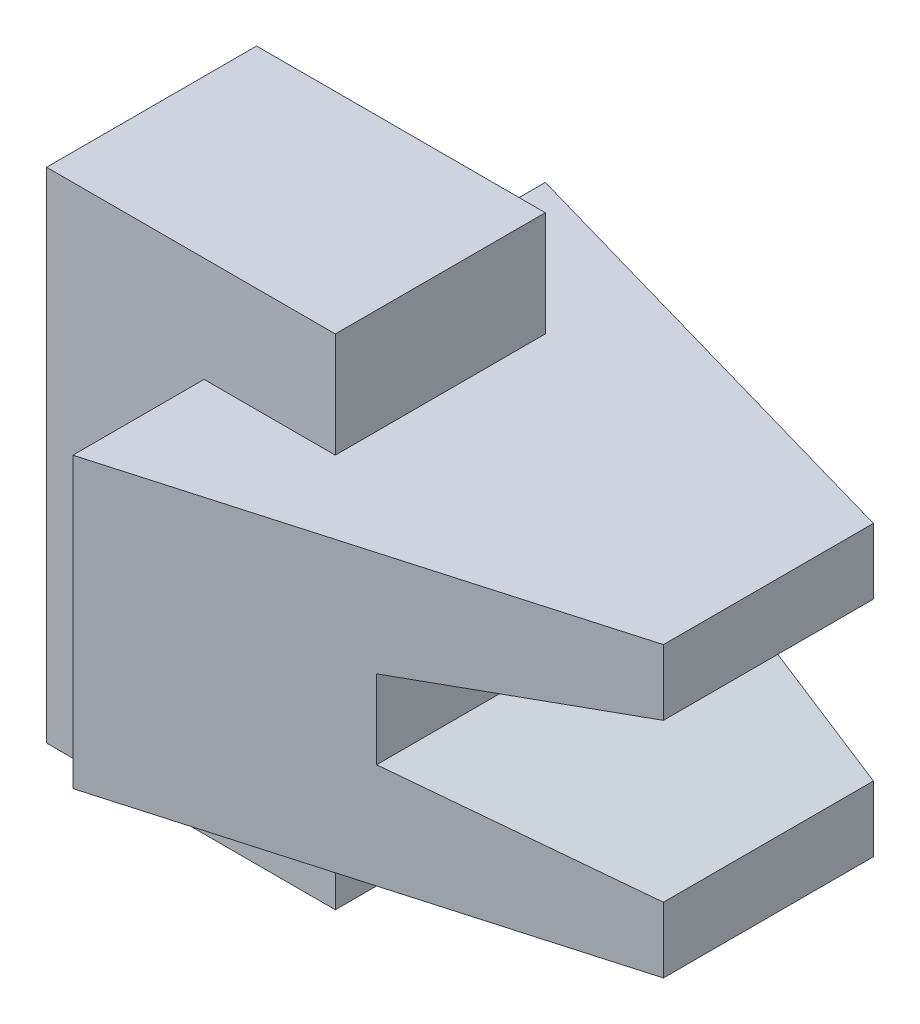
SolidWorks part; units mm, degrees
ref_plane "Front Plane" through (0, 0, 0) normal (0, 0, 1) x (1, 0, 0)
ref_plane "Top Plane" through (0, 0, 0) normal (0, 1, 0) x (1, 0, 0)
ref_plane "Right Plane" through (0, 0, 0) normal (1, 0, 0) x (0, 0, -1)
sketch "Sketch1" plane through (0, 0, 0) normal (0, 1, 0) x (1, 0, 0)
  line L0 (-27.7219, 18) -> (-27.7219, -18)
  line L1 (-27.7219, -18) -> (7.2781, -8)
  line L2 (7.2781, -8) -> (7.2781, 8)
  line L3 (7.2781, 8) -> (-27.7219, 18)
  point P3 (-27.7219, 0)
  point P5 (7.2781, 0)
  dimension "D1" = 36
  dimension "D2" = 16
  dimension "D3" = 35
extrude "Boss-Extrude1" add sketch "Sketch1" along normal blind 22
sketch "Sketch2" plane through (0, 0, 0) normal (0, 0, 1) x (1, 0, 0)
  line L0 (-9.7219, 14) -> (-9.7219, 8)
  line L1 (7.2781, 17) -> (7.2781, 5)
  line L2 (7.2781, 22) -> (7.2781, 0) construction
  line L3 (7.2781, 11) -> (-27.7219, 11) construction
  line L4 (-27.7219, 22) -> (-27.7219, 0) construction
  line L5 (-9.7219, 14) -> (7.2781, 17)
  line L6 (-9.7219, 8) -> (7.2781, 5)
  point P10 (-9.7219, 11)
  point P11 (7.2781, 11)
  dimension "D1" = 6
  dimension "D2" = 12
  dimension "D3" = 17
extrude "Cut-Extrude1" cut sketch "Sketch2" against normal through all both and the other way through all
sketch "Sketch3" plane through (0, 0, 0) normal (0, 0, 1) x (1, 0, 0)
  line L0 (-39.7219, 30) -> (-39.7219, -8)
  line L1 (-27.7219, 22) -> (-27.7219, 0) construction
  line L2 (7.2781, 5) -> (7.2781, 0) construction
  line L3 (-39.7219, 30) -> (-17.7219, 30)
  line L4 (-17.7219, 30) -> (-17.7219, 22)
  line L5 (-27.7219, 22) -> (7.2781, 22) construction
  line L6 (-17.7219, 22) -> (-27.7219, 22)
  line L7 (-27.7219, 22) -> (-27.7219, 0)
  line L8 (-27.7219, 0) -> (-17.7219, 0)
  line L9 (-27.7219, 0) -> (7.2781, 0) construction
  line L10 (-17.7219, 0) -> (-17.7219, -8)
  line L11 (-17.7219, -8) -> (-39.7219, -8)
  point P2 (-39.7219, 11)
  point P5 (-27.7219, 11)
  dimension "D1" = 38
  dimension "D2" = 47
  dimension "D3" = 22
extrude "Boss-Extrude2" add sketch "Sketch3" along normal blind 8 and the other way blind 8
